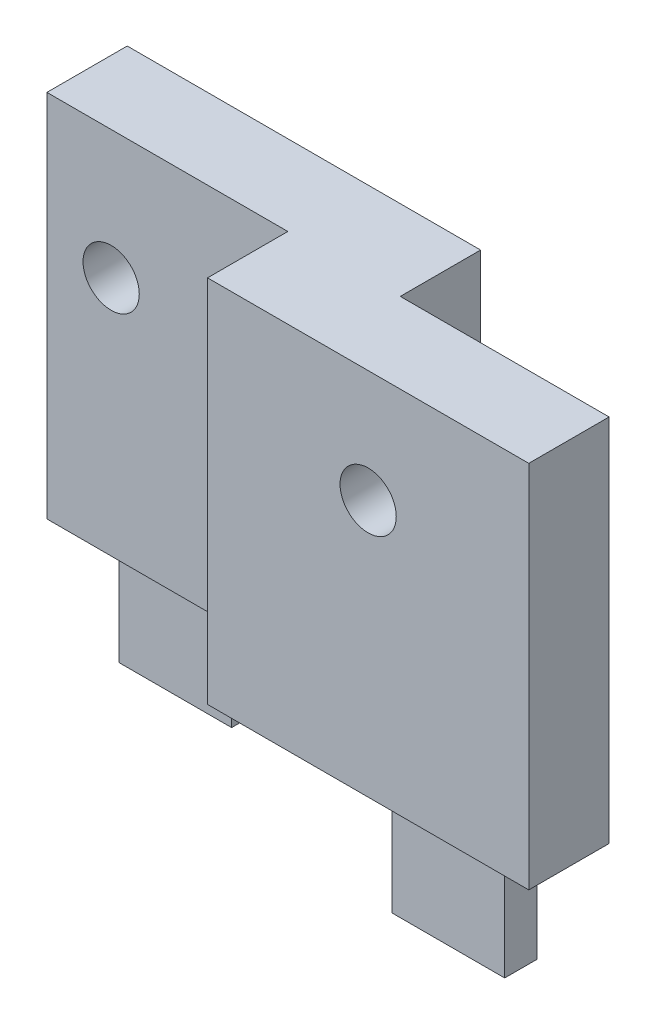
SolidWorks part; units mm, degrees
ref_plane "Front Plane" through (0, 0, 0) normal (0, 0, 1) x (1, 0, 0)
ref_plane "Top Plane" through (0, 0, 0) normal (0, 1, 0) x (1, 0, 0)
ref_plane "Right Plane" through (0, 0, 0) normal (1, 0, 0) x (0, 0, -1)
sketch "Sketch1" plane through (0, 0, 0) normal (0, 1, 0) x (1, 0, 0)
  line L0 (18, 0) -> (22, 0)
  line L1 (0, 0) -> (18, 0)
  line L2 (0, 0) -> (0, -5)
  line L3 (0, -5) -> (15, -5)
  line L5 (22, -5) -> (35, -5)
  line L6 (15, -5) -> (15, -10)
  line L7 (15, -10) -> (35, -10)
  line L8 (35, -5) -> (35, -10)
  line L9 (22, 0) -> (22, -5)
  line L10 (18, 0) -> (18, -10) construction
  dimension "D1" = 5
  dimension "D2" = 18
  dimension "D3" = 5
  dimension "D4" = 7
  dimension "D5" = 20
  dimension "D6" = 15
  dimension "D7" = 5
extrude "Boss-Extrude1" add sketch "Sketch1" along normal blind 23
sketch "Sketch2" plane through (0, 0, 10) normal (0, 0, 1) x (1, 0, 0)
  line L1 (15, 0) -> (35, 0) construction
  line L2 (35, 23) -> (35, 0) construction
  line L3 (0, 23) -> (0, 0) construction
  line L4 (0, 0) -> (15, 0) construction
  circle A0 centre (25, 16) radius 1.75
  circle A1 centre (4, 15) radius 1.75
  point P8 (27.3987, 11.5143)
  point P9 (25.9797, 7.0546)
  dimension "D1" = 3.5
  dimension "D2" = 3.5
  dimension "D3" = 10
  dimension "D4" = 16
  dimension "D5" = 4
  dimension "D6" = 15
extrude "Cut-Extrude1" cut sketch "Sketch2" against normal through all both and the other way through all
sketch "Sketch3" plane through (0, 0, 0) normal (0, -1, 0) x (1, 0, 0)
  line L0 (15, 5) -> (22, 5) construction
  line L1 (18.5, 5) -> (18.5, 10) construction
  line L2 (15, 10) -> (35, 10) construction
  line L3 (18.5, 5) -> (18.5, 0) construction
  line L4 (22, 0) -> (0, 0) construction
  circle A0 centre (18.5, 5) radius 1.5
  dimension "D1" = 3
extrude "Cut-Extrude2" cut sketch "Sketch3" against normal blind 10 and the other way through all
sketch "Sketch4" plane through (0, 0, 0) normal (0, -1, 0) x (1, 0, 0)
  line L0 (0, 2.5) -> (22, 2.5) construction
  line L1 (0, 0) -> (0, 5) construction
  line L2 (22, 5) -> (22, 0) construction
  line L3 (15, 7.5) -> (35, 7.5) construction
  line L4 (15, 5) -> (15, 10) construction
  line L5 (35, 10) -> (35, 5) construction
  line L7 (10, 1.5) -> (3, 1.5)
  line L8 (10, 1.5) -> (10, 3.5)
  line L9 (10, 3.5) -> (3, 3.5)
  line L10 (3, 1.5) -> (3, 3.5)
  line L11 (10, 1.5) -> (3, 3.5) construction
  line L12 (10, 3.5) -> (3, 1.5) construction
  line L13 (25, 6.5) -> (32, 6.5)
  line L14 (25, 6.5) -> (25, 8.5)
  line L15 (25, 8.5) -> (32, 8.5)
  line L16 (32, 6.5) -> (32, 8.5)
  line L17 (25, 6.5) -> (32, 8.5) construction
  line L18 (25, 8.5) -> (32, 6.5) construction
  point P12 (6.5, 2.5)
  point P17 (28.5, 7.5)
  dimension "D1" = 3
  dimension "D2" = 7
  dimension "D3" = 2
  dimension "D4" = 7
  dimension "D5" = 3
  dimension "D6" = 2
extrude "Boss-Extrude2" add sketch "Sketch4" along normal blind 7
